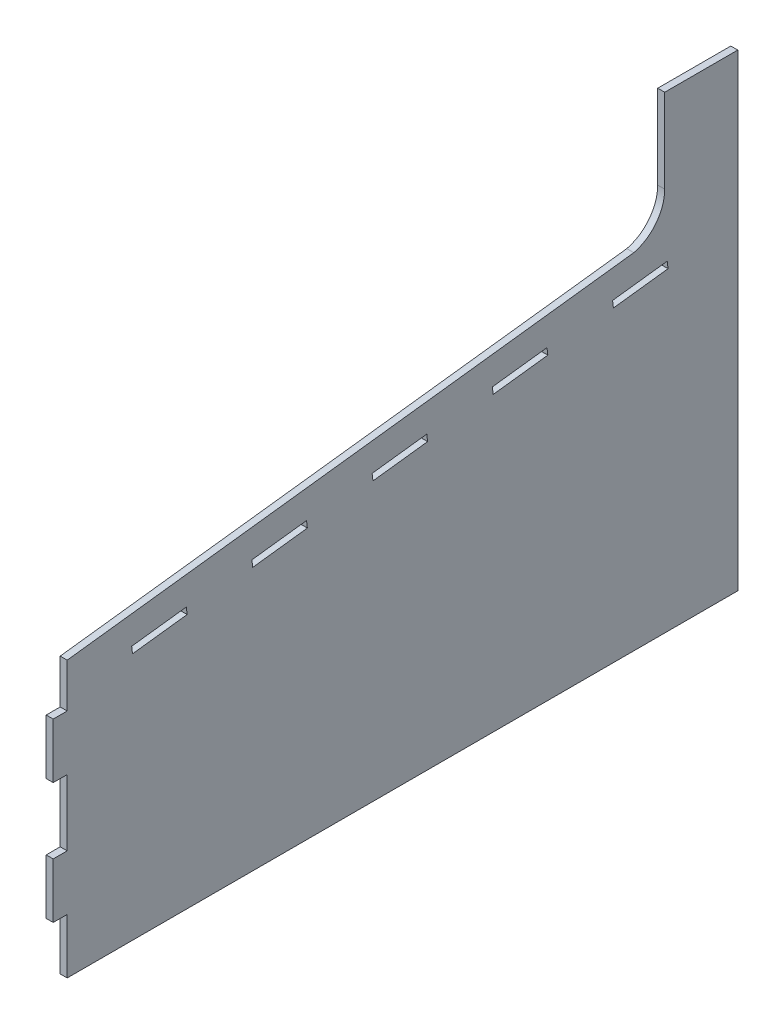
SolidWorks part; units mm, degrees
material "Beech"
ref_plane "Front Plane" through (0, 0, 0) normal (0, 0, 1) x (1, 0, 0)
ref_plane "Top Plane" through (0, 0, 0) normal (0, 1, 0) x (1, 0, 0)
ref_plane "Right Plane" through (0, 0, 0) normal (1, 0, 0) x (0, 0, -1)
sketch "Sketch1" plane through (0, 0, 0) normal (1, 0, 0) x (0, 0, -1)
  line L0 (0, 250) -> (514.5695, 313.1812)
  line L1 (0, 0) -> (609, 0)
  line L2 (0, 0) -> (0, 50)
  line L4 (609, 0) -> (609, 250)
  line L6 (609, 250) -> (609, 425.32)
  line L7 (609, 425.32) -> (542.65, 425.32)
  line L8 (542.65, 349.09) -> (542.65, 425.32)
  line L9 (0, 250) -> (609, 250) construction
  line L10 (514.5695, 313.1812) -> (609, 324.7758) construction
  line L11 (-12.7, 160) -> (-12.7, 210)
  line L12 (0, 50) -> (-12.7, 50)
  line L14 (0, 100) -> (-12.7, 100)
  line L15 (-12.7, 50) -> (-12.7, 100)
  line L16 (0, 160) -> (-12.7, 160)
  line L18 (0, 210) -> (-12.7, 210)
  line L19 (0, 210) -> (0, 250)
  line L21 (0, 100) -> (0, 160)
  arc A0 (514.5695, 313.1812) -> (542.65, 349.09) centre (505.65, 349.09) ccw
  dimension "D4" = 37
  dimension "D1" = 609
  dimension "D2" = 250
  dimension "D3" = 66.35
  dimension "D5" = 7
  dimension "D6" = 175.32
  dimension "D7" = 76.23
  dimension "D8" = 12.7
  dimension "D9" = 50
  dimension "D10" = 50
  dimension "D11" = 2
  dimension "D12" = 40
extrude "Boss-Extrude1" add sketch "Sketch1" along normal blind 6.35
sketch "Sketch2" plane through (6.35, 0, 0) normal (1, 0, 0) x (0, 0, -1)
  line L0 (514.5695, 313.1812) -> (609, 324.7758) construction
  line L1 (609, 0) -> (609, 425.32) construction
  line L2 (514.5695, 313.1812) -> (0, 250) construction
  line L3 (0, 224.4093) -> (609, 299.185) construction
  line L4 (0, 50) -> (0, 0) construction
  line L5 (58.5602, 231.5995) -> (59.3341, 225.2969)
  line L6 (59.3341, 225.2969) -> (108.9614, 231.3903)
  line L7 (108.9614, 231.3903) -> (108.1875, 237.693)
  line L8 (108.1875, 237.693) -> (58.5602, 231.5995)
  line L9 (217.3676, 251.0986) -> (167.7403, 245.0052)
  line L10 (167.7403, 245.0052) -> (168.5142, 238.7025)
  line L11 (168.5142, 238.7025) -> (218.1415, 244.796)
  line L12 (218.1415, 244.796) -> (217.3676, 251.0986)
  line L13 (326.5477, 264.5043) -> (276.9204, 258.4108)
  line L14 (276.9204, 258.4108) -> (277.6942, 252.1081)
  line L15 (277.6942, 252.1081) -> (327.3216, 258.2016)
  line L16 (327.3216, 258.2016) -> (326.5477, 264.5043)
  line L17 (435.7278, 277.9099) -> (386.1005, 271.8164)
  line L18 (386.1005, 271.8164) -> (386.8743, 265.5138)
  line L19 (386.8743, 265.5138) -> (436.5016, 271.6072)
  line L20 (436.5016, 271.6072) -> (435.7278, 277.9099)
  line L21 (544.9078, 291.3155) -> (495.2805, 285.2221)
  line L22 (495.2805, 285.2221) -> (496.0544, 278.9194)
  line L23 (496.0544, 278.9194) -> (545.6817, 285.0129)
  line L24 (545.6817, 285.0129) -> (544.9078, 291.3155)
  dimension "D1" = 25.4
  dimension "D2" = 50
  dimension "D3" = 6.35
  dimension "D4" = 59
extrude "Cut-Extrude1" cut sketch "Sketch2" against normal blind 6.35
